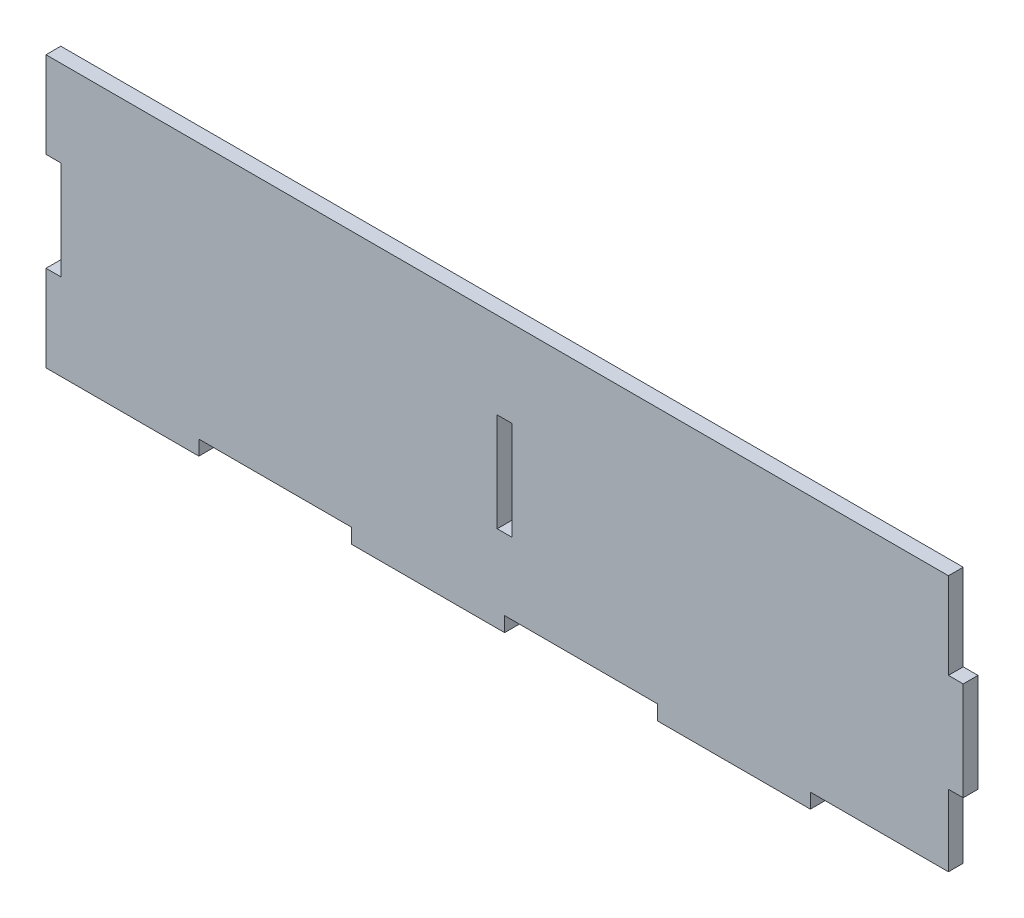
SolidWorks part; units mm, degrees
ref_plane "Front Plane" through (0, 0, 0) normal (0, 0, 1) x (1, 0, 0)
ref_plane "Top Plane" through (0, 0, 0) normal (0, 1, 0) x (1, 0, 0)
ref_plane "Right Plane" through (0, 0, 0) normal (1, 0, 0) x (0, 0, -1)
sketch "Sketch1" plane through (0, 0, 0) normal (0, 0, 1) x (1, 0, 0)
  line L0 (-93, 10) -> (-90, 10)
  line L1 (-93, -27.5) -> (93, -27.5)
  line L2 (-93, -27.5) -> (-93, 27.5)
  line L3 (-93, 27.5) -> (93, 27.5)
  line L4 (93, -27.5) -> (93, 27.5)
  line L5 (-93, -27.5) -> (93, 27.5) construction
  line L6 (-93, 27.5) -> (93, -27.5) construction
  line L7 (-90, 10) -> (-90, -10)
  line L8 (-90, -10) -> (-93, -10)
  line L9 (93, -10) -> (90, -10)
  line L10 (90, -10) -> (90, -27.5)
  line L11 (93, 10) -> (90, 10)
  line L12 (90, 10) -> (90, 27.5)
  line L14 (-62, -27.5) -> (-62, -24.5)
  line L15 (-62, -24.5) -> (-31, -24.5)
  line L16 (-31, -24.5) -> (-31, -27.5)
  line L18 (0, -27.5) -> (0, -24.5)
  line L19 (0, -24.5) -> (31, -24.5)
  line L20 (31, -24.5) -> (31, -27.5)
  line L22 (62, -27.5) -> (62, -24.5)
  line L23 (62, -24.5) -> (93, -24.5)
  line L24 (93, -24.5) -> (93, -27.5)
  line L26 (-1.5, -10) -> (1.5, -10)
  line L27 (-1.5, -10) -> (-1.5, 10)
  line L28 (-1.5, 10) -> (1.5, 10)
  line L29 (1.5, -10) -> (1.5, 10)
  line L30 (-1.5, -10) -> (1.5, 10) construction
  line L31 (-1.5, 10) -> (1.5, -10) construction
  point P0 (0, 0)
  point P15 (0, 0)
  dimension "D1" = 55
  dimension "D2" = 186
  dimension "D3" = 20
  dimension "D4" = 3
  dimension "D5" = 17.5
  dimension "D6" = 3
  dimension "D7" = 3
  dimension "D8" = 31
  dimension "D9" = 31
  dimension "D10" = 31
  dimension "D11" = 31
  dimension "D12" = 31
  dimension "D13" = 31
  dimension "D14" = 3
  dimension "D15" = 20
  dimension "D16" = 3
extrude "Boss-Extrude1" add sketch "Sketch1" along normal blind 3 contours L23 L24 L1 L10 L9 L4 L11 L12 L3 L2 L0 L7 L8 L14 L15 L16 L18 L19 L20 L22 L29 L26 L27 L28 region at (-91.0604, 18.75, 0)
